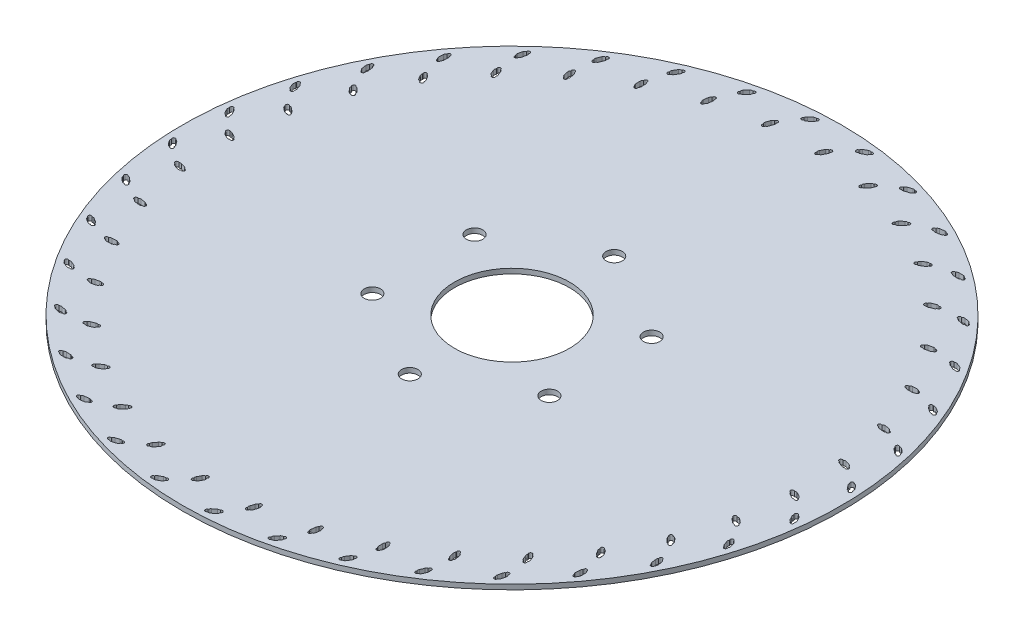
SolidWorks part; units mm, degrees
material "Steel Sectional "
ref_plane "Front Plane" through (0, 0, 0) normal (0, 0, 1) x (1, 0, 0)
ref_plane "Top Plane" through (0, 0, 0) normal (0, 1, 0) x (1, 0, 0)
ref_plane "Right Plane" through (0, 0, 0) normal (1, 0, 0) x (0, 0, -1)
sketch "Sketch1" plane through (0, 0, 0) normal (0, 1, 0) x (1, 0, 0)
  circle A0 centre (0, 0) radius 201.5
  circle A1 centre (0, 0) radius 35.15
  circle A2 centre (0, -62.5) radius 5
  circle A3 centre (-54.1266, -31.25) radius 5
  circle A4 centre (-54.1266, 31.25) radius 5
  circle A5 centre (0, 62.5) radius 5
  circle A6 centre (54.1266, 31.25) radius 5
  circle A7 centre (54.1266, -31.25) radius 5
  circle A8 centre (0, 0) radius 62.5 construction
  point P18 (0, 0)
  dimension "D1" = 403
  dimension "D2" = 70.3
  dimension "D3" = 10
  dimension "D4" = 62.5
  dimension "D6" = 125
  dimension "D5" = 6
sheet metal parameters "Sheet-Metal1" thickness 3 parameters "D1"=1, "厚度"=3
base flange "Base-Flange1" sketch "Sketch1" thickness 3 reverse thickness direction no parameters "D1"=1
sketch "Sketch6" plane through (0, -3, 0) normal (0, -1, 0) x (1, 0, 0)
  line L5 (177.1117, -24.4302) -> (176.8199, -22.9589) construction
  line L6 (183.4761, -20.7923) -> (184.1064, -22.1535) construction
  line L7 (188.8611, -19.4171) -> (171.0818, 5.9777) construction
  arc A0 (166.2916, -24.65) -> (201.5, 0) centre (171.0818, 5.9777) ccw construction
  arc A1 (184.1064, -22.1535) -> (193.0591, -15.8855) centre (171.0818, 5.9777) ccw construction
  arc A2 (166.4075, -23.909) -> (200.7641, 0.1446) centre (171.0818, 5.9777) ccw construction
  arc A3 (178.7144, -21.585) -> (177.6125, -22.5885) centre (179.1547, -23.1752) ccw
  arc A4 (177.6125, -22.5885) -> (178.0628, -24.4122) centre (177.5043, -23.5827) ccw
  arc A5 (183.3269, -22.6987) -> (182.6174, -20.9595) centre (183.2901, -21.6994) ccw
  arc A6 (182.296, -23.8862) -> (183.3269, -22.6987) centre (181.716, -22.3415) ccw
  arc A8 (179.5951, -24.7654) -> (182.296, -23.8862) centre (171.0818, 5.9777) ccw
  arc A9 (192.4466, -14.0778) -> (192.8006, -12.6302) centre (194.0536, -13.7037) cw
  arc A10 (197.2492, -10.9794) -> (197.0568, -12.5401) centre (195.7133, -11.5823) cw
  arc A11 (194.3698, -10.6244) -> (192.8006, -12.6302) centre (171.0818, 5.9777) cw
  arc A12 (197.0568, -12.5401) -> (195.3067, -14.7772) centre (171.0818, 5.9777) cw
  arc A13 (178.7144, -21.585) -> (181.1359, -20.7968) centre (171.0818, 5.9777) ccw
  arc A14 (195.3067, -14.7772) -> (193.8382, -15.3396) centre (194.0536, -13.7037) cw
  arc A15 (166.6625, -22.2788) -> (199.145, 0.4628) centre (171.0818, 5.9777) ccw construction
  arc A16 (166.1526, -25.5392) -> (202.3831, -0.1735) centre (171.0818, 5.9777) ccw construction
  arc A17 (178.0628, -24.4122) -> (179.5951, -24.7654) centre (179.1547, -23.1752) ccw
  arc A18 (182.6174, -20.9595) -> (181.1359, -20.7968) centre (181.716, -22.3415) ccw
  arc A19 (193.8382, -15.3396) -> (192.4466, -14.0778) centre (192.9117, -14.9631) cw
  arc A20 (195.6897, -9.9324) -> (197.2492, -10.9794) centre (196.6609, -10.1708) cw
  arc A21 (194.3698, -10.6244) -> (195.6897, -9.9324) centre (195.7133, -11.5823) cw
  dimension "D3" = 2
  dimension "D2" = 3.3
  dimension "D6" = 1.7
  dimension "D7" = 1.7
  dimension "D4" = 0.55
  dimension "D5" = 0.55
  dimension "D1" = 0.75
  dimension "D8" = 1.65
  dimension "D9" = 1.65
extrude "Extrude1" cut sketch "Sketch6" against normal blind 10 normal cut yes
pattern_circular "CirPattern1" count 36 over 360 about axis through (0, 0, 0) along (0, 1, 0) of "Extrude1"
flat pattern "Flat-Pattern1" [suppressed]
sketch "Sketch3" plane through (0, 0, 0) normal (0, 1, 0) x (1, 0, 0)
sketch "Sketch5" [suppressed] plane through (0, 0, 0) normal (0, 1, 0) x (1, 0, 0)
